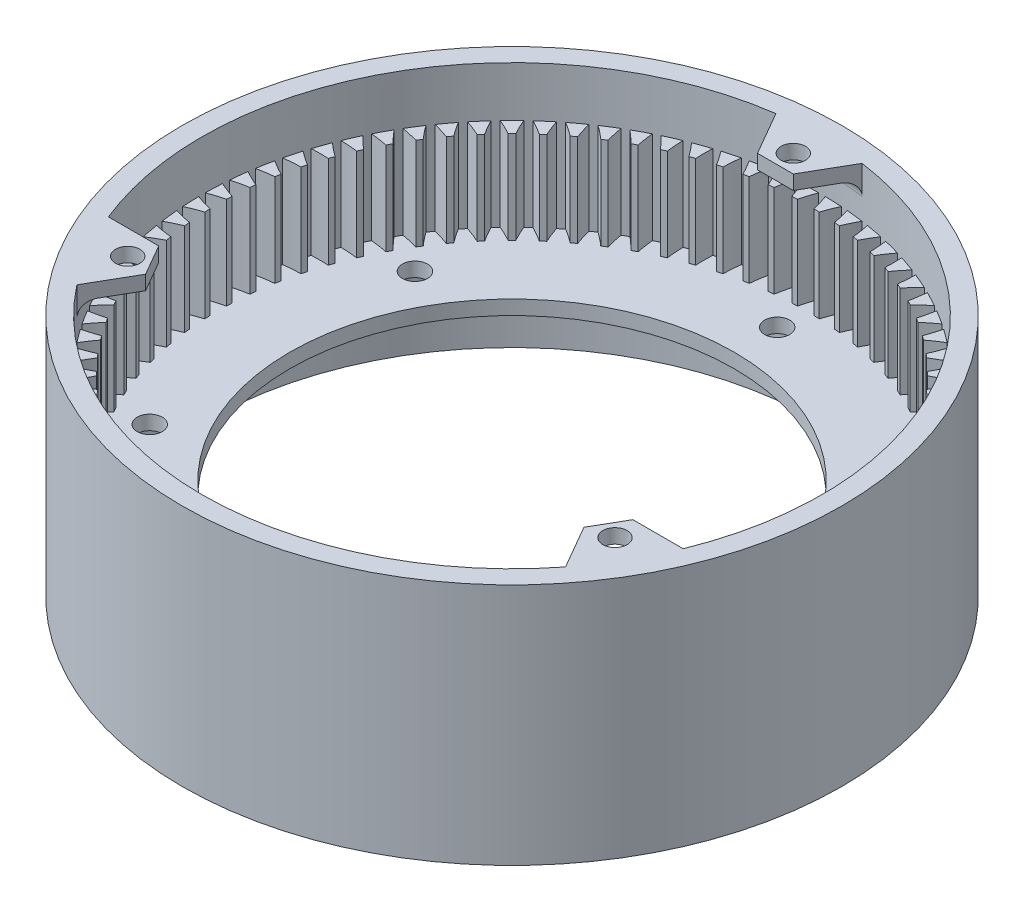
SolidWorks part; units mm, degrees
material "PLA"
ref_plane "Front Plane" through (0, 0, 0) normal (0, 0, 1) x (1, 0, 0)
ref_plane "Top Plane" through (0, 0, 0) normal (0, 1, 0) x (1, 0, 0)
ref_plane "Right Plane" through (0, 0, 0) normal (1, 0, 0) x (0, 0, -1)
sketch "Sketch1" plane through (0, 0, 0) normal (0, 1, 0) x (1, 0, 0)
  circle A0 centre (0, 0) radius 42 construction
  dimension "D1" = 84
sketch "Sketch2" plane through (0, 0, 0) normal (0, 0, 1) x (1, 0, 0)
  line L0 (0, -536.8627) -> (0, 26306.2717) construction
sketch "Sketch3" plane through (0, 0, 0) normal (1, 0, 0) x (0, 0, -1)
  line L0 (-923.3838, 0) -> (45245.8085, 0) construction
  line L2 (-46, -6.45) -> (-41, -6.45)
  line L3 (-46, -6.45) -> (-46, 6.45)
  line L4 (-46, 6.45) -> (-41, 6.45)
  line L5 (-41, -6.45) -> (-41, 6.45)
  line L6 (-46, -6.45) -> (-41, 6.45) construction
  line L7 (-46, 6.45) -> (-41, -6.45) construction
  point P1 (-43.5, 0)
  dimension "D1" = 12.9
  dimension "D2" = 46
  dimension "D3" = 41
revolve "Revolve1" add sketch "Sketch3" angle 360 about L0
sketch "Sketch4" plane through (0, 6.45, 0) normal (0, 1, 0) x (1, 0, 0)
  line L0 (0, -1000) -> (0, 49000) construction
  arc B0 (1.1647, 40.958) -> (0.4555, 43.2486) centre (-19.2177, 35.9025) ccw
  arc B1 (1.1647, 40.958) -> (-1.1647, 40.958) centre (0, 0) ccw
  arc B2 (0.4555, 43.2486) -> (-0.4555, 43.2486) centre (0, 0) ccw
  arc B3 (-0.4555, 43.2486) -> (-1.1647, 40.958) centre (19.2177, 35.9025) ccw
  dimension "D1" = 40.9746
sketch_block_instance "Block1-1"
sketch_block "Block1"
extrude "Cut-Extrude1" cut sketch "Sketch4" against normal up to surface (12.9 mm away) up to face at (41, -6.45, 0)
pattern_circular "CirPattern1" count 84 over 360 about axis through (0, 6.45, 0) along (0, -1, 0) of "Cut-Extrude1"
sketch "Sketch5" plane through (0, -6.45, 0) normal (0, -1, 0) x (1, 0, 0)
  line L0 (0, -1000) -> (0, 49000) construction
  circle A0 centre (0, 0) radius 31
  circle A1 centre (0, 0) radius 46
  circle A2 centre (0, 0) radius 46 construction
  circle A3 centre (0, 0) radius 37 construction
  circle A4 centre (0, 37) radius 1.75
  circle A5 centre (32.0429, 18.5) radius 1.75
  circle A6 centre (32.0429, -18.5) radius 1.75
  circle A7 centre (0, -37) radius 1.75
  circle A8 centre (-32.0429, -18.5) radius 1.75
  circle A9 centre (-32.0429, 18.5) radius 1.75
  point P23 (0, 0)
  dimension "D1" = 62
  dimension "D2" = 74
  dimension "D3" = 3.5
  dimension "D4" = 6
extrude "Boss-Extrude2" add sketch "Sketch5" along normal blind 2
sketch "Sketch6" plane through (0, -8.45, 0) normal (0, -1, 0) x (1, 0, 0)
  circle A0 centre (0, 0) radius 46
  circle A1 centre (0, 0) radius 46 construction
  circle A2 centre (0, 0) radius 42.5
  dimension "D1" = 85
extrude "Boss-Extrude3" add sketch "Sketch6" along normal blind 12
sketch "Sketch7" plane through (0, 6.45, 0) normal (0, 1, 0) x (1, 0, 0)
  circle A0 centre (0, 0) radius 43.251
  arc A1 (-37.2267, 22.0187) -> (-37.6821, 21.2299) centre (0, 0) ccw construction
  circle A2 centre (0, 0) radius 46
  circle A3 centre (0, 0) radius 46 construction
extrude "Boss-Extrude4" add sketch "Sketch7" along normal blind 7
sketch "Sketch8" plane through (0, 13.45, 0) normal (0, 1, 0) x (1, 0, 0)
  circle A0 centre (0, 0) radius 46
  circle A1 centre (0, 0) radius 32
  circle A2 centre (0, 0) radius 46 construction
  dimension "D1" = 64
sketch "Sketch9" plane through (0, 13.45, 0) normal (0, 1, 0) x (1, 0, 0)
  line L0 (0, -1000) -> (0, 49000) construction
  line L1 (0, 0) -> (-43301.2702, -25000) construction
  line L2 (0, 0) -> (43301.2702, -25000) construction
  line L3 (-6.0105, 42.8313) -> (-2.5, 36.751)
  line L4 (-2.5, 36.751) -> (2.5, 36.751)
  line L5 (2.5, 36.751) -> (6.0105, 42.8313)
  arc A0 (-2.7778, 43.1617) -> (-3.6862, 43.0936) centre (0, 0) ccw construction
  arc A1 (3.6862, 43.0936) -> (2.7778, 43.1617) centre (0, 0) ccw construction
  circle A2 centre (0, 0) radius 43.251 construction
  arc A3 (-6.0105, 42.8313) -> (6.0105, 42.8313) centre (0, 0) cw
  circle A4 centre (0, 39.251) radius 1.7
  circle A5 centre (0, 0) radius 46 construction
  point P25 (0, 36.751)
  point P27 (0, 43.251)
  point P29 (0, 46)
  dimension "D1" = 3.4
  dimension "D2" = 4
  dimension "D3" = 5
  dimension "D4" = 6.5
  dimension "D5" = 120
extrude "Boss-Extrude5" add sketch "Sketch9" against normal blind 2
pattern_circular "CirPattern2" count 3 over 360 about axis through (0, 13.45, 0) along (0, 1, 0) of "Boss-Extrude5"
fillet "Fillet1" radius 2 3 edges at (-37.4565, 11.45, 21.6255) (0, 11.45, -43.251) (37.4565, 11.45, 21.6255)
